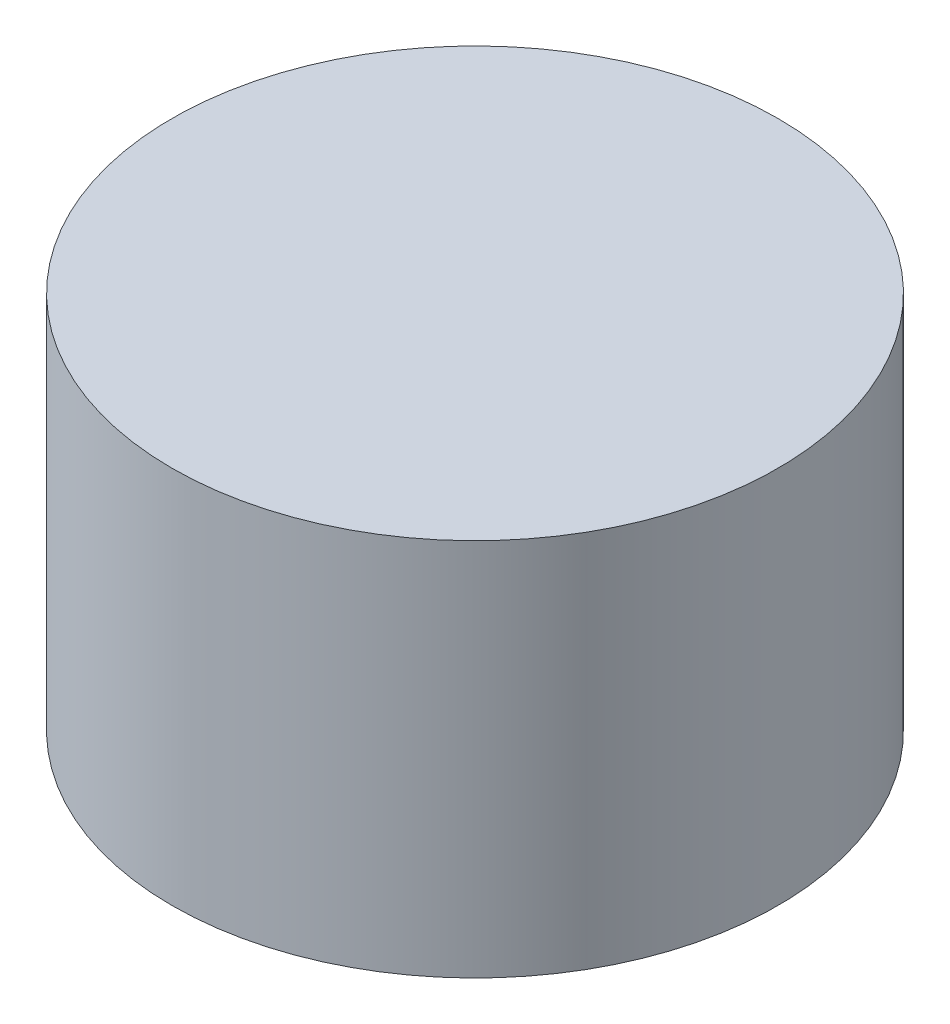
SolidWorks part; units mm, degrees
ref_plane "前视基准面" through (0, 0, 0) normal (0, 0, 1) x (1, 0, 0)
ref_plane "上视基准面" through (0, 0, 0) normal (0, 1, 0) x (1, 0, 0)
ref_plane "右视基准面" through (0, 0, 0) normal (1, 0, 0) x (0, 0, -1)
ref_plane "LEDTop" through (0, 0, 0) normal (0, 1, 0) x (1, 0, 0)
ref_plane "CenterV" through (0, 0, 0) normal (1, 0, 0) x (0, 0, -1)
ref_plane "CenterH" through (0, 0, 0) normal (0, 0, 1) x (1, 0, 0)
sketch "Circle" plane through (0, 0, 0) normal (0, 1, 0) x (1, 0, 0)
  line L0 (0, 0) -> (-200, 0) construction
  dimension "R" = 200
ref_axis "CenterAxis" through (-200, 0, 0) along (0, 1, 0)
sketch "SRectangle" [suppressed] plane through (0, 0, 0) normal (0, 1, 0) x (1, 0, 0)
  line L1 (-0.5, -2.5) -> (0.5, -2.5)
  line L2 (-0.5, -2.5) -> (-0.5, 2.5)
  line L3 (-0.5, 2.5) -> (0.5, 2.5)
  line L4 (0.5, -2.5) -> (0.5, 2.5)
  line L5 (-0.5, -2.5) -> (0.5, 2.5) construction
  line L6 (-0.5, 2.5) -> (0.5, -2.5) construction
  point P0 (0, 0)
  dimension "D1" = 1
  dimension "D2" = 5
extrude "FRectangle" [suppressed] add sketch "SRectangle" against normal blind 5
sketch "RectangleCut" [suppressed] plane through (0, 0, 0) normal (0, 1, 0) x (1, 0, 0)
  line L4 (-0.5, -2.5) -> (0.5, -2.5)
  line L5 (0.5, -2.5) -> (0.5, 2.5)
  line L6 (0.5, 2.5) -> (-0.5, 2.5)
  line L7 (-0.5, 2.5) -> (-0.5, -2.5)
  line L8 (-0.5, -2.5) -> (0.5, -2.5)
  line L9 (0.5, -2.5) -> (0.5, 2.5)
  line L10 (0.5, 2.5) -> (-0.5, 2.5)
  line L11 (-0.5, 2.5) -> (-0.5, -2.5)
  dimension "D1" = 0
sketch "SRound" plane through (0, 0, 0) normal (0, 1, 0) x (1, 0, 0)
  circle A0 centre (0, 0) radius 4
  dimension "D1" = 8
extrude "FRound" add sketch "SRound" against normal blind 5
sketch "RoundCut" plane through (0, 0, 0) normal (0, 1, 0) x (1, 0, 0)
  circle A1 centre (0, 0) radius 4
  circle A2 centre (0, 0) radius 4
  dimension "D1" = 0
equation "\"LedH\"= 5"
equation "\"D1@FRectangle\"=\"LedH\""
equation "\"D1@FRound\"=\"LedH\""
